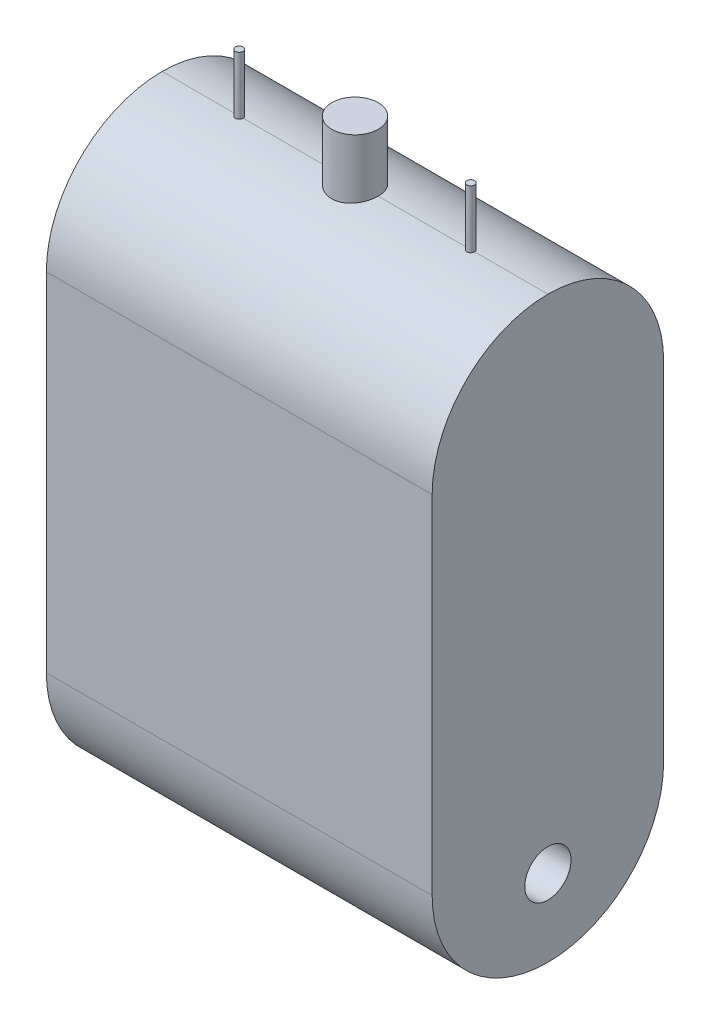
SolidWorks part; units mm, degrees
ref_plane "前视基准面" through (0, 0, 0) normal (0, 0, 1) x (1, 0, 0)
ref_plane "上视基准面" through (0, 0, 0) normal (0, 1, 0) x (1, 0, 0)
ref_plane "右视基准面" through (0, 0, 0) normal (1, 0, 0) x (0, 0, -1)
sketch "草图1" plane through (0, 0, 0) normal (0, 0, 1) x (1, 0, 0)
  line L0 (0, 0) -> (25, 0) construction
  line L1 (25, 0) -> (25, 42.5)
  line L2 (25, 42.5) -> (-25, 42.5)
  line L3 (-25, 42.5) -> (-25, -32.5)
  line L4 (-25, -32.5) -> (25, -32.5)
  line L5 (25, -32.5) -> (25, 0)
  dimension "D1" = 25
  dimension "D2" = 42.5
  dimension "D3" = 50
  dimension "D4" = 75
extrude "凸台-拉伸1" add sketch "草图1" along normal blind 30
sketch "草图2" plane through (25, 0, 0) normal (1, 0, 0) x (0, 0, -1)
  line L0 (0, -32.5) -> (0, -22.5) construction
  line L1 (0, -32.5) -> (0, 42.5) construction
  line L2 (0, -22.5) -> (-15, -22.5) construction
  circle A0 centre (-15, -22.5) radius 3
  dimension "D3" = 6
  dimension "D1" = 10
  dimension "D2" = 15
extrude "切除-拉伸1" cut sketch "草图2" against normal blind 52
fillet "圆角1" radius 15 1 edges at (0, -32.5, 0)
fillet "圆角2" radius 15 3 edges at (0, -32.5, 30) (25, -32.5, 22.5) (-25, -32.5, 22.5)
fillet "圆角3" radius 15 1 edges at (0, 42.5, 30)
fillet "圆角4" radius 15 3 edges at (-25, 42.5, 7.5) (25, 42.5, 7.5) (0, 42.5, 0)
sketch "草图4" plane through (0, 0, 0) normal (0, 1, 0) x (1, 0, 0)
  line L0 (-25, -15) -> (25, -15) construction
  line L1 (0, -15) -> (-15, -15) construction
  line L2 (0, -15) -> (15, -15) construction
  circle A0 centre (0, -15) radius 3
  circle A2 centre (15, -15) radius 0.5
  circle A3 centre (-15, -15) radius 0.5
  dimension "D1" = 6
  dimension "D2" = 15
  dimension "D3" = 1
  dimension "D5" = 1
  dimension "D4" = 15
extrude "凸台-拉伸2" add sketch "草图4" along normal blind 50
sketch "草图5" plane through (0, 0, 30) normal (0, 0, 1) x (1, 0, 0)
  line L0 (0, 27.5) -> (0, -17.5) construction
  line L1 (25, 27.5) -> (-25, 27.5) construction
  line L2 (-25, -17.5) -> (25, -17.5) construction
  line L3 (15, 5) -> (-15, 5) construction
  circle A0 centre (0, 5) radius 3
  circle A1 centre (-15, 5) radius 0.5
  circle A2 centre (15, 5) radius 0.5
  point P10 (0, 0)
  dimension "D1" = 6
  dimension "D3" = 1
  dimension "D2" = 15
extrude "凸台-拉伸3" add sketch "草图5" against normal blind 37
